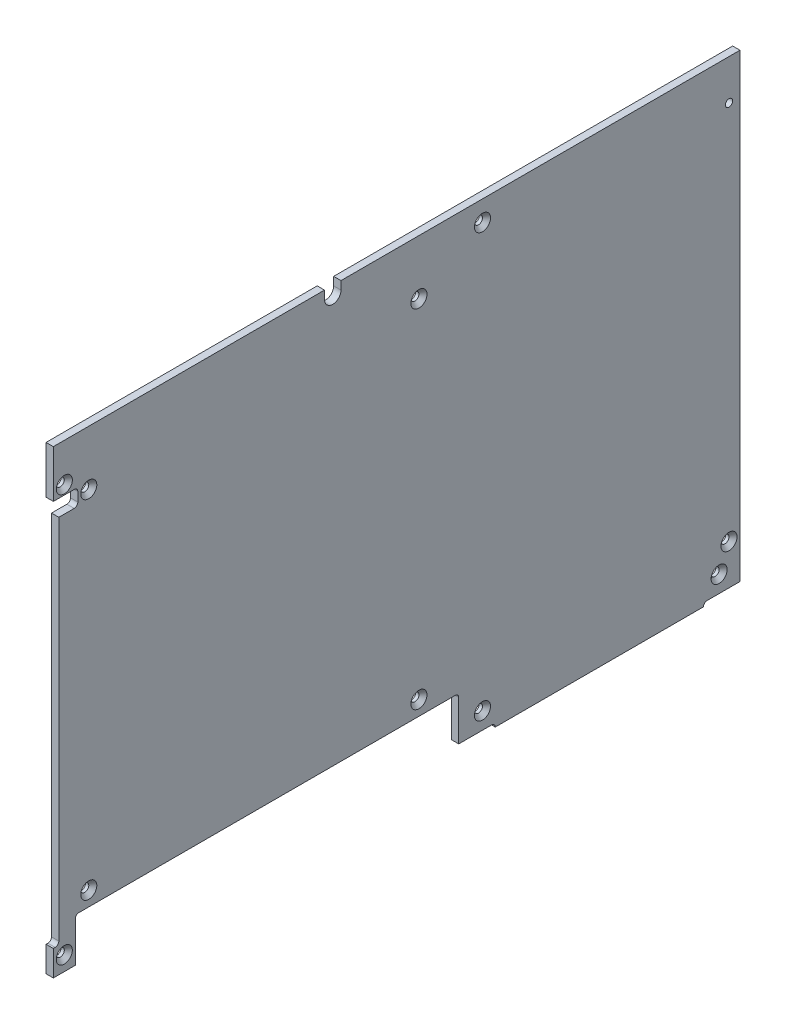
SolidWorks part; units mm, degrees
material "AISI 304"
ref_plane "前视基准面" through (0, 0, 0) normal (0, 0, 1) x (1, 0, 0)
ref_plane "上视基准面" through (0, 0, 0) normal (0, 1, 0) x (1, 0, 0)
ref_plane "右视基准面" through (0, 0, 0) normal (1, 0, 0) x (0, 0, -1)
sketch "草图1" plane through (0, 0, 0) normal (1, 0, 0) x (0, 0, -1)
  line L1 (-157.8453, 143.2715) -> (30.1547, 143.2715)
  line L2 (-157.8453, 143.2715) -> (-157.8453, -6.7285)
  line L3 (-157.8453, -6.7285) -> (30.1547, -6.7285)
  line L4 (30.1547, 143.2715) -> (30.1547, -6.7285)
  dimension "D1" = 188
  dimension "D2" = 150
extrude "凸台-拉伸1" add sketch "草图1" along normal blind 2
sketch "草图13" plane through (2, 0, 0) normal (1, 0, 0) x (0, 0, -1)
  line L1 (-157.8453, 143.2715) -> (30.1547, 143.2715)
  line L2 (-157.8453, 143.2715) -> (-157.8453, 131.2715)
  line L3 (-157.8453, 131.2715) -> (30.1547, 131.2715)
  line L4 (30.1547, 143.2715) -> (30.1547, 131.2715)
  line L5 (30.1547, -6.7285) -> (30.1547, 143.2715) construction
  dimension "D1" = 0
  dimension "D2" = 12
extrude "切除-拉伸8" cut sketch "草图13" against normal blind 11
sketch "草图5" plane through (0, 0, 0) normal (-1, 0, 0) x (0, 0, 1)
  line L0 (157.8453, 131.2715) -> (-30.1547, 131.2715) construction
  line L1 (46.0453, 131.2715) -> (-30.1547, 131.2715) construction
  line L2 (46.0453, 131.2715) -> (46.0453, 4.2715) construction
  line L3 (46.0453, 4.2715) -> (-30.1547, 4.2715) construction
  line L4 (-30.1547, 131.2715) -> (-30.1547, 4.2715) construction
  line L5 (-30.1547, -6.7285) -> (-30.1547, 131.2715) construction
  line L7 (-24.4547, 125.6715) -> (40.3453, 125.6715) construction
  line L8 (-24.4547, 125.6715) -> (-24.4547, 9.8715) construction
  line L9 (-24.4547, 9.8715) -> (40.3453, 9.8715) construction
  line L10 (40.3453, 125.6715) -> (40.3453, 9.8715) construction
  circle A0 centre (-24.4547, 125.6715) radius 1 construction
  circle A1 centre (40.3453, 125.6715) radius 1
  circle A2 centre (-24.4547, 9.8715) radius 1
  circle A3 centre (40.3453, 9.8715) radius 1
  dimension "D1" = 76.2
  dimension "D2" = 5.6
  dimension "D3" = 5.7
  dimension "D4" = 64.8
  dimension "D5" = 115.8
  dimension "D9" = 127
  dimension "D10" = 0
  dimension "D11" = 0
extrude "EPP" cut sketch "草图5" against normal blind 2
sketch "草图6" plane through (0, 0, 0) normal (-1, 0, 0) x (0, 0, 1)
  line L0 (157.8453, 131.2715) -> (-30.1547, 131.2715) construction
  line L1 (57.7453, 116.2715) -> (148.1453, 116.2715) construction
  line L2 (57.7453, 116.2715) -> (57.7453, 21.2715) construction
  line L3 (57.7453, 21.2715) -> (148.1453, 21.2715) construction
  line L4 (148.1453, 116.2715) -> (148.1453, 21.2715) construction
  line L5 (157.8453, 131.2715) -> (157.8453, -6.7285) construction
  circle A0 centre (57.7453, 116.2715) radius 1
  circle A1 centre (148.1453, 116.2715) radius 1
  circle A2 centre (57.7453, 21.2715) radius 1
  circle A3 centre (148.1453, 21.2715) radius 1
  dimension "D1" = 90.4
  dimension "D2" = 95
  dimension "D3" = 15
  dimension "D4" = 9.7
extrude "切除-拉伸4" cut sketch "草图6" against normal blind 2
sketch "草图7" plane through (0, 0, 0) normal (-1, 0, 0) x (0, 0, 1)
  line L0 (61.2453, 25.2715) -> (61.2453, 18.2715)
  line L1 (37.7453, 112.2715) -> (61.2453, 112.2715)
  line L2 (37.7453, 112.2715) -> (37.7453, 25.2715)
  line L3 (37.7453, 25.2715) -> (61.2453, 25.2715)
  line L4 (156.6453, 112.2715) -> (156.6453, 25.2715)
  line L5 (61.2453, 119.2715) -> (144.6453, 119.2715)
  line L6 (61.2453, 119.2715) -> (61.2453, 112.2715)
  line L7 (61.2453, 18.2715) -> (144.6453, 18.2715)
  line L8 (144.6453, 119.2715) -> (144.6453, 112.2715)
  line L9 (144.6453, 25.2715) -> (144.6453, 18.2715)
  line L10 (144.6453, 112.2715) -> (156.6453, 112.2715)
  line L11 (144.6453, 25.2715) -> (156.6453, 25.2715)
  circle A0 centre (57.7453, 116.2715) radius 1 construction
  circle A1 centre (57.7453, 21.2715) radius 1 construction
  circle A2 centre (148.1453, 116.2715) radius 1 construction
  circle A3 centre (148.1453, 21.2715) radius 1 construction
  circle A4 centre (57.7453, 21.2715) radius 1 construction
  point P22 (49.4953, 25.2715)
  dimension "D1" = 4
  dimension "D2" = 3
  dimension "D4" = 8.5
  dimension "D3" = 20
  dimension "D5" = 3
  dimension "D6" = 4
  dimension "D7" = 3.5
  dimension "D8" = 3.5
extrude "切除-拉伸5" [suppressed] cut sketch "草图7" against normal blind 2
sketch "草图3" plane through (0, 0, 0) normal (-1, 0, 0) x (0, 0, 1)
  line L0 (157.8453, -6.7285) -> (-30.1547, -6.7285) construction
  line L1 (-30.1547, -6.7285) -> (46.8453, -6.7285)
  line L2 (-30.1547, -6.7285) -> (-30.1547, 4.2715)
  line L3 (-20.1547, 4.2715) -> (36.8453, 4.2715)
  line L4 (46.8453, -6.7285) -> (46.8453, 4.2715)
  line L5 (-30.1547, -6.7285) -> (-30.1547, 131.2715) construction
  line L7 (157.8453, 131.2715) -> (-30.1547, 131.2715) construction
  line L10 (-30.1547, 4.2715) -> (-30.1547, 5.2715)
  line L11 (-30.1547, 5.2715) -> (-20.1547, 5.2715)
  line L12 (-20.1547, 4.2715) -> (-20.1547, 5.2715)
  line L13 (46.8453, 4.2715) -> (46.8453, 5.2715)
  line L14 (46.8453, 5.2715) -> (36.8453, 5.2715)
  line L15 (36.8453, 4.2715) -> (36.8453, 5.2715)
  dimension "D1" = 0
  dimension "D2" = 77
  dimension "D3" = 127
extrude "B-FAN" cut sketch "草图3" against normal blind 2
sketch "草图10" plane through (0, 0, 0) normal (-1, 0, 0) x (0, 0, 1)
  line L0 (46.8453, 5.2715) -> (46.8453, -6.7285)
  line L6 (151.8453, 5.2715) -> (157.8453, 5.2715)
  line L9 (46.8453, 17.2715) -> (151.8453, 17.2715)
  line L10 (151.8453, 5.2715) -> (151.8453, 17.2715)
  line L11 (46.8453, -6.7285) -> (157.8453, -6.7285)
  line L13 (157.8453, -6.7285) -> (157.8453, 5.2715)
  line L20 (46.8453, 5.2715) -> (46.8453, 17.2715)
  line L22 (157.8453, 131.2715) -> (157.8453, -6.7285) construction
  dimension "D1" = 12
  dimension "D2" = 6
  dimension "D3" = 12
extrude "PCI-E" cut sketch "草图10" against normal blind 2
sketch "草图14" plane through (0, 0, 0) normal (-1, 0, 0) x (0, 0, 1)
  line L0 (-30.1547, 5.2715) -> (-30.1547, 131.2715) construction
  line L2 (-27.1547, 120.2715) -> (-27.1547, 16.2715) construction
  line L4 (154.8453, 120.7715) -> (154.8453, 9.2715) construction
  line L5 (157.8453, 131.2715) -> (-30.1547, 131.2715) construction
  line L6 (157.8453, 131.2715) -> (157.8453, 5.2715) construction
  line L7 (157.8453, 5.2715) -> (151.8453, 5.2715) construction
  line L9 (157.8453, 131.2715) -> (-30.1547, 131.2715) construction
  line L12 (-20.1547, 5.2715) -> (-30.1547, 5.2715) construction
  circle A1 centre (154.8453, 120.7715) radius 1
  circle A2 centre (154.8453, 9.2715) radius 1
  circle A3 centre (-27.1547, 16.2715) radius 1
  circle A4 centre (-27.1547, 120.2715) radius 1
  dimension "D1" = 3
  dimension "D4" = 10.5
  dimension "D2" = 11
  dimension "D3" = 3
  dimension "D5" = 11
  dimension "D6" = 4
extrude "机箱螺孔" cut sketch "草图14" against normal blind 5
sketch "草图15" plane through (0, 0, 0) normal (-1, 0, 0) x (0, 0, 1)
  line L0 (157.8453, 131.2715) -> (157.8453, 5.2715) construction
  line L1 (157.8453, 118.2715) -> (156.3453, 118.2715)
  line L2 (157.8453, 118.2715) -> (157.8453, 12.2715)
  line L3 (157.8453, 12.2715) -> (156.3453, 12.2715)
  line L4 (156.3453, 113.7715) -> (156.3453, 12.2715)
  line L5 (157.8453, 131.2715) -> (-30.1547, 131.2715) construction
  line L6 (157.8453, 5.2715) -> (151.8453, 5.2715) construction
  line L16 (156.3453, 113.7715) -> (151.1453, 113.7715)
  line L18 (156.3453, 118.2715) -> (151.1453, 118.2715)
  line L19 (151.1453, 113.7715) -> (151.1453, 118.2715)
  circle A0 centre (148.1453, 116.2715) radius 1 construction
  point P10 (153.1453, 113.7715)
  point P12 (153.1453, 113.8501)
  dimension "D4" = 3
  dimension "D1" = 13
  dimension "D2" = 7
  dimension "D3" = 1.5
  dimension "D6" = 101.5
extrude "减去IO厚度" cut sketch "草图15" against normal blind 10
hole_wizard "打孔尺寸(%根据)内六角花形沉头螺钉的类型1" positions "草图16" profile "草图17" countersink size "M6" standard "GB" end condition through all
sketch "草图16" plane through (2, 0, 0) normal (1, 0, 0) x (0, 0, -1)
  point P0 (-40.3453, 125.6715)
  point P6 (-40.3453, 9.8715)
  point P9 (24.4547, 9.8715)
  point P12 (-57.7453, 21.2715)
  point P15 (-148.1453, 21.2715)
  point P18 (-148.1453, 116.2715)
  point P21 (-57.7453, 116.2715)
  point P24 (-154.8453, 120.7715)
  point P27 (-154.8453, 9.2715)
  point P30 (27.1547, 16.2715)
sketch "草图17" plane through (2, 125.6715, 40.3453) normal (0, 1, 0) x (0, 0, -1)
  line L0 (0, 0) -> (0, 2)
  line L1 (0, 2) -> (1.1, 2)
  line L2 (1.1, 2) -> (1.1, 1.1)
  line L3 (1.1, 1.1) -> (2.2, 0)
  line L5 (2.2, 0) -> (0, 0)
  line L6 (-1.1, 1.1) -> (-2.2, 0) construction
  line L11 (0, -6.35) -> (0, 107.95) construction
  dimension "通孔孔直径" = 2.2
  dimension "通孔孔深度" = 2
  dimension "近端锥形沉头孔直径" = 4.4
  dimension "近端锥形沉头孔角度" = 90
sketch "草图21" [suppressed] plane through (2, 0, 0) normal (1, 0, 0) x (0, 0, -1)
  line L0 (-37.7453, 112.2715) -> (-37.7453, 25.2715) construction
  line L1 (-25.7453, 112.2715) -> (18.1547, 112.2715)
  line L2 (-25.7453, 112.2715) -> (-25.7453, 25.2715)
  line L3 (-25.7453, 25.2715) -> (18.1547, 25.2715)
  line L4 (18.1547, 112.2715) -> (18.1547, 25.2715)
  line L5 (30.1547, 5.2715) -> (30.1547, 131.2715) construction
  line L6 (-46.8453, 4.2715) -> (21.4547, 4.2715) construction
  line L7 (-156.3453, 131.2715) -> (30.1547, 131.2715) construction
  dimension "D1" = 12
  dimension "D2" = 12
  dimension "D3" = 21
  dimension "D4" = 19
extrude "切除-拉伸12" [suppressed] cut sketch "草图21" against normal blind 10
fillet "圆角1" [suppressed] radius 1
sketch "草图23" plane through (0, 0, 0) normal (-1, 0, 0) x (0, 0, 1)
  line L3 (81.3453, 133.5215) -> (81.3453, 129.0215) construction
  line L4 (83.5953, 133.5215) -> (83.5953, 129.0215)
  line L5 (79.0953, 133.5215) -> (79.0953, 129.0215)
  line L6 (157.8453, 131.2715) -> (157.8453, 118.2715) construction
  line L7 (157.8453, 131.2715) -> (-30.1547, 131.2715) construction
  arc A1 (83.5953, 133.5215) -> (79.0953, 133.5215) centre (81.3453, 133.5215) ccw
  arc A2 (79.0953, 129.0215) -> (83.5953, 129.0215) centre (81.3453, 129.0215) ccw
  point P2 (81.3453, 131.2715)
  dimension "D1" = 76.5
extrude "切除-拉伸14" cut sketch "草图23" against normal blind 10
fillet "圆角2" radius 1 7 edges at (1, 113.7715, 151.1453) (1, 118.2715, 151.1453) (1, 12.2715, 156.3453) (1, 17.2715, 151.8453) (1, 17.2715, 46.8453) (1, 5.2715, 36.8453) (1, 5.2715, -20.1547)
